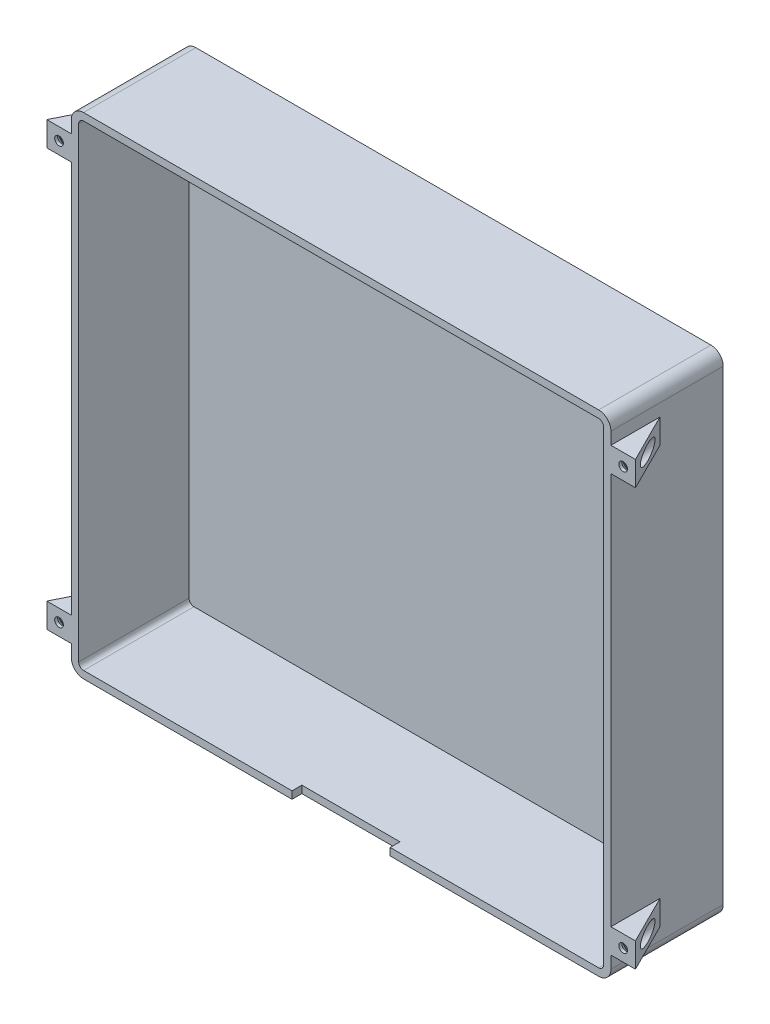
SolidWorks part; units mm, degrees
ref_plane "Front Plane" through (0, 0, 0) normal (0, 0, 1) x (1, 0, 0)
ref_plane "Top Plane" through (0, 0, 0) normal (0, 1, 0) x (1, 0, 0)
ref_plane "Right Plane" through (0, 0, 0) normal (1, 0, 0) x (0, 0, -1)
sketch "Sketch2" plane through (0, 0, 0) normal (0, 0, 1) x (1, 0, 0)
  line L5 (139.7, 127) -> (-139.7, 127)
  line L6 (139.7, 127) -> (139.7, -127)
  line L7 (139.7, -127) -> (-139.7, -127)
  line L8 (-139.7, 127) -> (-139.7, -127)
  line L9 (139.7, 127) -> (-139.7, -127) construction
  line L10 (139.7, -127) -> (-139.7, 127) construction
  point P0 (0, 0)
  dimension "D1" = 254
  dimension "D2" = 279.4
extrude "Boss-Extrude1" add sketch "Sketch2" along normal blind 1
fillet "Fillet2" radius 6.35 4 edges at (139.7, -127, 0.5) (-139.7, -127, 0.5) (-139.7, 127, 0.5) (139.7, 127, 0.5)
sketch "Sketch5" plane through (0, 0, 1) normal (0, 0, 1) x (1, 0, 0)
  line L0 (-133.35, -123.19) -> (133.35, -123.19)
  line L1 (135.89, -120.65) -> (135.89, 120.65)
  line L2 (133.35, 123.19) -> (-133.35, 123.19)
  line L3 (-135.89, 120.65) -> (-135.89, -120.65)
  line L4 (-133.35, -127) -> (133.35, -127)
  line L5 (139.7, -120.65) -> (139.7, 120.65)
  line L6 (133.35, 127) -> (-133.35, 127)
  line L7 (-139.7, 120.65) -> (-139.7, -120.65)
  line L8 (-133.35, -127) -> (133.35, -127)
  line L9 (139.7, -120.65) -> (139.7, 120.65)
  line L10 (133.35, 127) -> (-133.35, 127)
  line L11 (-139.7, 120.65) -> (-139.7, -120.65)
  arc A0 (133.35, -123.19) -> (135.89, -120.65) centre (133.35, -120.65) ccw
  arc A1 (135.89, 120.65) -> (133.35, 123.19) centre (133.35, 120.65) ccw
  arc A2 (-133.35, 123.19) -> (-135.89, 120.65) centre (-133.35, 120.65) ccw
  arc A3 (-135.89, -120.65) -> (-133.35, -123.19) centre (-133.35, -120.65) ccw
  arc A4 (133.35, -127) -> (139.7, -120.65) centre (133.35, -120.65) ccw
  arc A5 (139.7, 120.65) -> (133.35, 127) centre (133.35, 120.65) ccw
  arc A6 (-133.35, 127) -> (-139.7, 120.65) centre (-133.35, 120.65) ccw
  arc A7 (-139.7, -120.65) -> (-133.35, -127) centre (-133.35, -120.65) ccw
  arc A8 (133.35, -127) -> (139.7, -120.65) centre (133.35, -120.65) ccw
  arc A9 (139.7, 120.65) -> (133.35, 127) centre (133.35, 120.65) ccw
  arc A10 (-133.35, 127) -> (-139.7, 120.65) centre (-133.35, 120.65) ccw
  arc A11 (-139.7, -120.65) -> (-133.35, -127) centre (-133.35, -120.65) ccw
  dimension "D1" = 0
  dimension "D2" = 3.81
extrude "Boss-Extrude3" add sketch "Sketch5" along normal blind 57.15
sketch "Sketch7" plane through (0, -123.19, 0) normal (0, 1, 0) x (1, 0, 0)
  line L0 (-133.35, -58.15) -> (133.35, -58.15) construction
  line L1 (25.4, -58.15) -> (-25.4, -58.15)
  line L2 (25.4, -58.15) -> (25.4, -53.07)
  line L3 (25.4, -53.07) -> (-25.4, -53.07)
  line L4 (-25.4, -58.15) -> (-25.4, -53.07)
  point P6 (0, -58.15)
  dimension "D1" = 5.08
  dimension "D2" = 50.8
extrude "Cut-Extrude1" cut sketch "Sketch7" against normal blind 57.15
ref_plane "Plane1" through (0, 101.6, 0) normal (0, 1, 0) x (1, 0, 0)
sketch "Sketch8" plane through (0, 101.6, 0) normal (0, 1, 0) x (1, 0, 0)
  line L0 (-139.7, 0) -> (-152.4, 0)
  line L1 (-152.4, 0) -> (-139.7, -25.4)
  line L2 (-139.7, -58.15) -> (-139.7, 0) construction
  line L3 (-139.7, -25.4) -> (-139.7, 0)
  line L4 (139.7, 0) -> (139.7, -25.4) construction
  line L5 (139.7, 0) -> (139.7, -58.15) construction
  line L6 (139.7, -25.4) -> (152.4, 0) construction
  line L7 (152.4, 0) -> (139.7, 0) construction
  dimension "D1" = 12.7
  dimension "D2" = 25.4
extrude "Boss-Extrude4" add sketch "Sketch8" along normal blind 12.7
ref_plane "Plane2" through (0, 0, 3.81) normal (0, 0, -1) x (-1, 0, 0)
sketch "Sketch9" plane through (0, 0, 3.81) normal (0, 0, -1) x (-1, 0, 0)
  line L0 (152.4, 114.3) -> (152.4, 101.6) construction
  line L1 (152.4, 114.3) -> (152.4, 101.6)
  line L2 (152.4, 107.95) -> (146.05, 107.95)
  circle A0 centre (146.05, 107.95) radius 3.81
  dimension "D1" = 7.62
  dimension "D2" = 6.35
extrude "Cut-Extrude2" cut sketch "Sketch9" against normal blind 35.306 contours A0
hole_wizard "CSK for #8 Flat Head Machine Screw1" positions "Sketch12" profile "Sketch13" countersink size "#8" standard "ANSI Inch" end condition through all
sketch "Sketch12" plane through (0, 0, 3.81) normal (0, 0, 1) x (1, 0, 0)
  point P0 (-146.05, 107.95)
sketch "Sketch13" plane through (-146.05, 107.95, 3.81) normal (1, 0, 0) x (0, -1, 0)
  line L0 (0, 0) -> (0, 3.81)
  line L1 (0, 3.81) -> (2.2479, 3.81)
  line L2 (2.2479, 3.81) -> (2.2479, 2.2645)
  line L3 (2.2479, 2.2645) -> (4.2164, 0)
  line L5 (4.2164, 0) -> (0, 0)
  line L6 (-2.2479, 2.2645) -> (-4.2164, 0) construction
  line L11 (0, -6.35) -> (0, 107.95) construction
  dimension "Thru Hole Dia." = 4.4958
  dimension "Thru Hole Depth" = 3.81
  dimension "Near C'Sink Dia." = 8.4328
  dimension "Near C'Sink Angle" = 82
sketch "Sketch14" plane through (0, 0, 3.81) normal (0, 0, -1) x (-1, 0, 0)
  line L1 (159.8523, 111.76) -> (146.05, 111.76)
  line L2 (159.8523, 111.76) -> (159.8523, 104.14)
  line L3 (159.8523, 104.14) -> (146.05, 104.14)
  line L4 (146.05, 111.76) -> (146.05, 104.14)
  circle A0 centre (146.05, 107.95) radius 2.2479 construction
  circle A1 centre (146.05, 107.95) radius 2.2479 construction
  circle A2 centre (146.05, 107.95) radius 3.81 construction
ref_plane "Plane3" through (0, 0, 0) normal (0, 1, 0) x (1, 0, 0)
mirror "Mirror2" about plane through (0, 0, 0) normal (0, 1, 0) of "Cut-Extrude2", "CSK for #8 Flat Head Machine Screw1", "Boss-Extrude4"
ref_plane "Plane4" through (0, 0, 0) normal (-1, 0, 0) x (0, 0, 1)
mirror "Mirror3" about plane through (0, 0, 0) normal (-1, 0, 0) of "Mirror2", "CSK for #8 Flat Head Machine Screw1", "Cut-Extrude2", "Boss-Extrude4"
ref_plane "Plane5" through (0, 0, 29.075) normal (0, 0, -1) x (-1, 0, 0)
mirror "Mirror4" about plane through (0, 0, 29.075) normal (0, 0, -1) of "Mirror3", "Mirror2", "CSK for #8 Flat Head Machine Screw1", "Cut-Extrude2", "Boss-Extrude4"
sketch "Sketch15" plane through (0, 0, 0) normal (0, 0, -1) x (-1, 0, 0)
  line L1 (-152.4, 114.3) -> (-139.7, 114.3)
  line L2 (-152.4, 114.3) -> (-152.4, -114.3)
  line L3 (-152.4, -114.3) -> (-139.7, -114.3)
  line L4 (-139.7, 114.3) -> (-139.7, -114.3)
  line L5 (152.4, -114.3) -> (139.7, -114.3)
  line L6 (152.4, -114.3) -> (152.4, 114.3)
  line L7 (152.4, 114.3) -> (139.7, 114.3)
  line L8 (139.7, -114.3) -> (139.7, 114.3)
extrude "Cut-Extrude4" cut sketch "Sketch15" against normal blind 30.226
sketch "Sketch17" [suppressed] plane through (0, 127, 0) normal (0, 1, 0) x (1, 0, 0)
  line L4 (98.4433, -33.0881) -> (98.4433, -48.0233)
  line L5 (98.4433, -48.0233) -> (119.2713, -48.0233)
  line L6 (119.2713, -48.0233) -> (119.2713, -33.0881)
  line L7 (119.2713, -33.0881) -> (98.4433, -33.0881)
  line L8 (98.4433, -33.0881) -> (98.4433, -48.0233)
  line L9 (98.4433, -48.0233) -> (119.2713, -48.0233)
  line L10 (119.2713, -48.0233) -> (119.2713, -33.0881)
  line L11 (119.2713, -33.0881) -> (98.4433, -33.0881)
  circle A0 centre (-108.6948, -25.9909) radius 1.632 construction
  circle A1 centre (-25.8908, -25.9909) radius 1.632 construction
  circle A2 centre (98.0996, -15.605) radius 6.9215 construction
  circle A3 centre (-108.6948, -25.9909) radius 1.632
  circle A4 centre (-25.8908, -25.9909) radius 1.632
  circle A5 centre (98.0996, -15.605) radius 6.9215
  dimension "D1" = 0
sketch "Sketch18" [suppressed] plane through (0, 123.19, 0) normal (0, -1, 0) x (1, 0, 0)
  line L0 (133.35, 1) -> (-133.35, 1) construction
  line L1 (-16.3658, 1) -> (-35.4158, 1)
  line L2 (-118.2198, 1) -> (-118.2198, 25.9909)
  line L3 (-99.1698, 25.9909) -> (-99.1698, 1)
  line L4 (-99.1698, 1) -> (-118.2198, 1)
  line L5 (-35.4158, 1) -> (-35.4158, 25.9909)
  line L6 (-16.3658, 25.9909) -> (-16.3658, 1)
  line L7 (-16.3658, 1) -> (-35.4158, 1)
  line L8 (-99.1698, 1) -> (-118.2198, 1)
  arc A2 (-118.2198, 25.9909) -> (-99.1698, 25.9909) centre (-108.6948, 25.9909) cw
  arc A3 (-35.4158, 25.9909) -> (-16.3658, 25.9909) centre (-25.8908, 25.9909) cw
  line M2 (-133.35, 1) -> (133.35, 1)
  dimension "D1" = 9.525
extrude "Boss-Extrude5" [suppressed] add sketch "Sketch18" along normal blind 12.7 contours A2 L2 L3 M2 | A3 L5 L6 M2
sketch "Sketch19" [suppressed] plane through (0, 127, 0) normal (0, 1, 0) x (1, 0, 0)
  circle A0 centre (-108.6948, -25.9909) radius 1.27
  circle A1 centre (-25.8908, -25.9909) radius 1.27
  dimension "D1" = 2.54
extrude "Cut-Extrude5" [suppressed] cut sketch "Sketch19" against normal up to next
